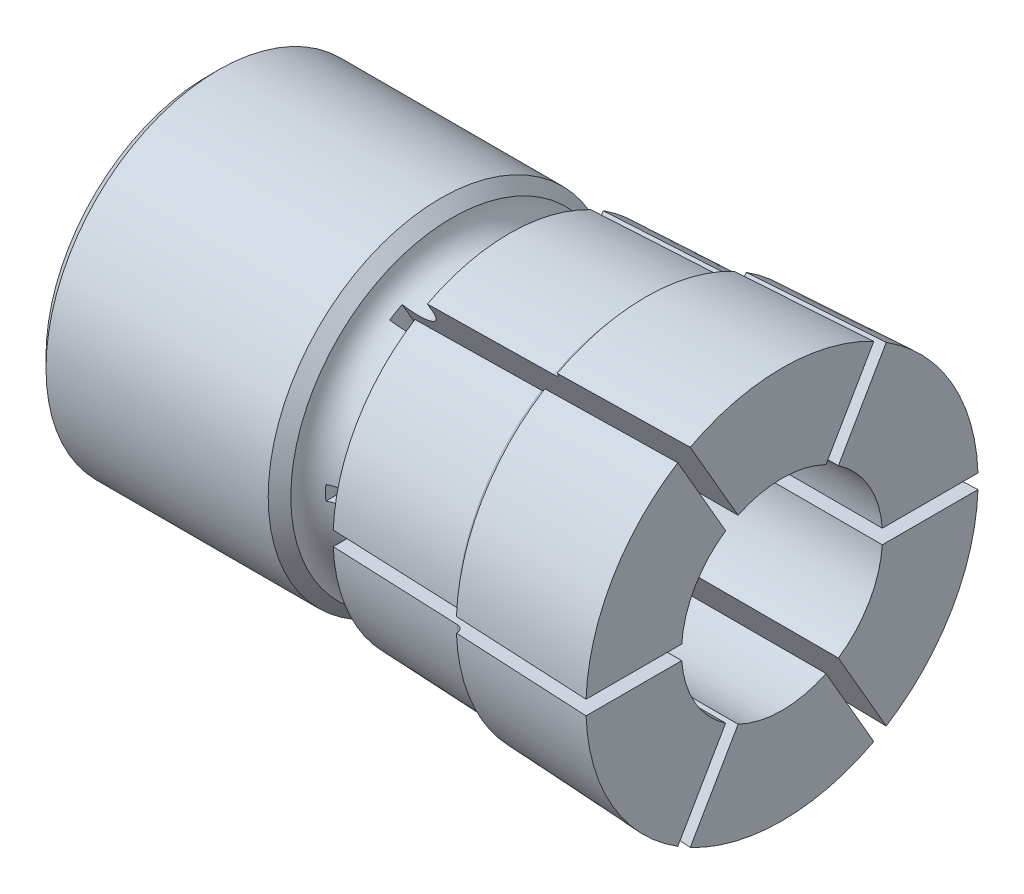
SolidWorks part; units mm, degrees
ref_plane "Front Plane" through (0, 0, 0) normal (0, 0, 1) x (1, 0, 0)
ref_plane "Top Plane" through (0, 0, 0) normal (0, 1, 0) x (1, 0, 0)
ref_plane "Right Plane" through (0, 0, 0) normal (1, 0, 0) x (0, 0, -1)
sketch "Sketch1" plane through (0, 0, 0) normal (0, 0, 1) x (1, 0, 0)
  line L0 (8.054, 0) -> (0, 4.65)
  line L1 (0, 4.65) -> (0, 11.233)
  line L2 (0, 11.233) -> (0.767, 12)
  line L3 (0.767, 12) -> (16.233, 12)
  line L4 (16.233, 12) -> (17.0208, 11.2122)
  line L5 (21, 11.5) -> (21, 12.25)
  line L6 (21, 12.25) -> (30.021, 12.6298)
  line L7 (30.5, 13.1294) -> (30.5, 13.175)
  line L8 (30.5, 13.175) -> (40, 13.65)
  line L9 (40, 13.65) -> (40, 0)
  line L10 (40, 0) -> (8.054, 0)
  line L11 (40, 0) -> (8.054, 0) construction
  arc A0 (17.0208, 11.2122) -> (21, 11.5) centre (19, 11.5) ccw
  arc A1 (30.021, 12.6298) -> (30.5, 13.1294) centre (30, 13.1294) ccw
revolve "Revolve1" add sketch "Sketch1" angle 360 about L11 reverse direction yes
cosmetic thread "Cosmetic Thread1" parameters "D1"=17, "D2"=22.466
ref_plane "Plane1" through (17.8, 0, 0) normal (1, 0, 0) x (0, 0, -1)
ref_plane "Plane2" through (22.5, 0, 0) normal (1, 0, 0) x (0, 0, -1)
ref_plane "Plane3" through (31, 0, 0) normal (1, 0, 0) x (0, 0, -1)
ref_plane "Plane4" through (33.1, 0, 0) normal (1, 0, 0) x (0, 0, -1)
ref_plane "Plane5" through (41.3, 0, 0) normal (1, 0, 0) x (0, 0, -1)
sketch "Sketch2" plane through (0, 0, 0) normal (1, 0, 0) x (0, 0, -1)
  line L0 (-4, -2.3094) -> (0, -4.6188)
  line L1 (0, -4.6188) -> (4, -2.3094)
  line L2 (4, -2.3094) -> (4, 2.3094)
  line L3 (4, 2.3094) -> (0, 4.6188)
  line L4 (0, 4.6188) -> (-4, 2.3094)
  line L5 (-4, 2.3094) -> (-4, -2.3094)
extrude "Cut-Extrude1" cut sketch "Sketch2" along normal blind 6
sketch "Sketch3" plane through (0, 0, 0) normal (0, 1, 0) x (1, 0, 0)
  line L0 (6, 0) -> (6, 4.75)
  line L1 (6, 4.75) -> (8, 4.75)
  line L2 (8, 4.75) -> (8, 3.5)
  line L3 (8, 3.5) -> (10, 3.5)
  line L4 (10, 3.5) -> (10, 7.2)
  line L5 (10, 7.2) -> (12, 7.2)
  line L6 (12, 7.2) -> (12, 7)
  line L7 (12, 7) -> (42, 7)
  line L8 (42, 7) -> (42, 0)
  line L9 (42, 0) -> (6, 0)
  line L10 (42, 0) -> (6, 0) construction
revolve "Cut-Revolve1" cut sketch "Sketch3" angle 360 about L10 reverse direction yes
ref_plane "Plane6" through (18, 0, 0) normal (1, 0, 0) x (0, 0, -1)
sketch "Sketch4" plane through (18, 0, 0) normal (1, 0, 0) x (0, 0, -1)
  line L0 (-18.65, 0.5) -> (-18.65, -0.5)
  line L1 (-18.65, -0.5) -> (-0.866, -0.5)
  line L2 (-0.866, -0.5) -> (-9.758, -15.9014)
  line L3 (-9.758, -15.9014) -> (-8.892, -16.4014)
  line L4 (-8.892, -16.4014) -> (0, -1)
  line L5 (0, -1) -> (8.892, -16.4014)
  line L6 (8.892, -16.4014) -> (9.758, -15.9014)
  line L7 (9.758, -15.9014) -> (0.866, -0.5)
  line L8 (0.866, -0.5) -> (18.65, -0.5)
  line L9 (18.65, -0.5) -> (18.65, 0.5)
  line L10 (18.65, 0.5) -> (0.866, 0.5)
  line L11 (0.866, 0.5) -> (9.758, 15.9014)
  line L12 (9.758, 15.9014) -> (8.892, 16.4014)
  line L13 (8.892, 16.4014) -> (0, 1)
  line L14 (0, 1) -> (-8.892, 16.4014)
  line L15 (-8.892, 16.4014) -> (-9.758, 15.9014)
  line L16 (-9.758, 15.9014) -> (-0.866, 0.5)
  line L17 (-0.866, 0.5) -> (-18.65, 0.5)
extrude "Cut-Extrude2" cut sketch "Sketch4" along normal blind 40
ref_plane "Plane7" through (40, 0, 0) normal (1, 0, 0) x (0, 0, -1)
ref_plane "ANBAU XY" through (40, 0, 0) normal (1, 0, 0) x (0, 0, -1)
ref_plane "ANBAU XZ" through (0, 0, 0) normal (0, -1, 0) x (-1, 0, 0)
ref_plane "ANBAU YZ" through (0, 0, 0) normal (0, 0, -1) x (-1, 0, 0)
ref_axis "ANBAU X" through (40, 0, 80.9) along (0, 0, -1)
ref_axis "ANBAU Y" through (40, -50, 0) along (0, 1, 0)
ref_axis "ANBAU Z" through (80.9, 0, 0) along (-1, 0, 0)
sketch3d "ANBAU"
  point P0 (40, 0, 0)
other "Freeze***"
